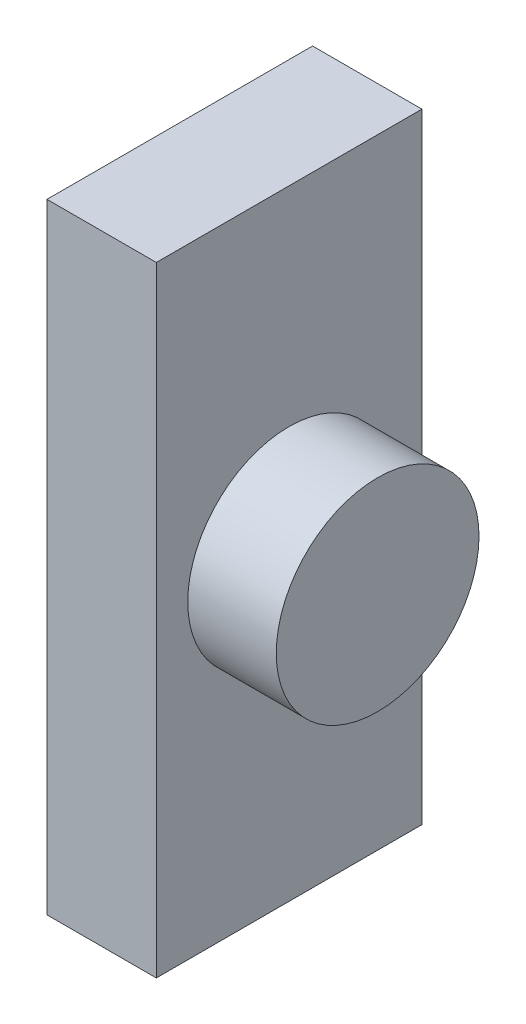
SolidWorks part; units mm, degrees
ref_plane "Front Plane" through (0, 0, 0) normal (0, 0, 1) x (1, 0, 0)
ref_plane "Top Plane" through (0, 0, 0) normal (0, 1, 0) x (1, 0, 0)
ref_plane "Right Plane" through (0, 0, 0) normal (1, 0, 0) x (0, 0, -1)
sketch "Sketch1" plane through (0, 0, 0) normal (1, 0, 0) x (0, 0, -1)
  line L0 (5.8625, 17.5) -> (9.1375, 17.5) construction
  line L1 (5.8625, 24) -> (9.1375, 24)
  line L2 (5.8625, 24) -> (5.8625, 11)
  line L3 (5.8625, 11) -> (9.1375, 11)
  line L4 (9.1375, 24) -> (9.1375, 11)
  line L5 (7.5, 24) -> (7.5, 11) construction
  line L6 (7.5, 35) -> (7.5, 0) construction
  line L15 (0, 35) -> (15, 35)
  line L16 (0, 35) -> (0, 0)
  line L17 (0, 0) -> (15, 0)
  line L18 (15, 35) -> (15, 0)
  line L19 (0, 17.5) -> (15, 17.5) construction
  dimension "D2" = 3.275
  dimension "D3" = 13
  dimension "D4" = 15
  dimension "D5" = 35
extrude "Boss-Extrude1" add sketch "Sketch1" along normal blind 4.175
sketch "Sketch2" plane through (4.175, 0, 0) normal (1, 0, 0) x (0, 0, -1)
  line L1 (0, 35) -> (15, 35)
  line L2 (0, 35) -> (0, 0)
  line L3 (0, 0) -> (15, 0)
  line L4 (15, 35) -> (15, 0)
extrude "Boss-Extrude2" add sketch "Sketch2" along normal blind 2
sketch "Sketch3" plane through (6.175, 0, 0) normal (1, 0, 0) x (0, 0, -1)
  line L0 (7.5, 35) -> (7.5, 0) construction
  line L1 (15, 35) -> (0, 35) construction
  line L2 (0, 0) -> (15, 0) construction
  line L3 (0, 17.5) -> (15, 17.5) construction
  line L4 (0, 35) -> (0, 0) construction
  line L5 (15, 0) -> (15, 35) construction
  circle A0 centre (7.5, 17.5) radius 5.725
  dimension "D1" = 11.45
extrude "Boss-Extrude3" add sketch "Sketch3" along normal blind 5
